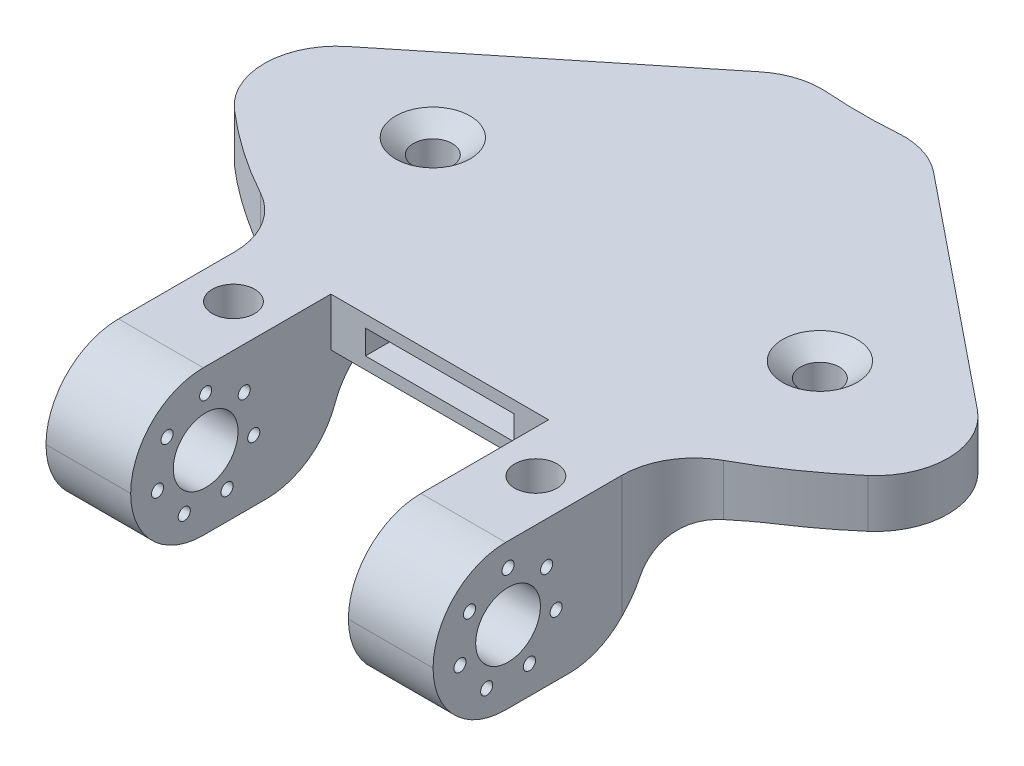
SolidWorks part; units mm, degrees
ref_plane "Front Plane" through (0, 0, 0) normal (0, 0, 1) x (1, 0, 0)
ref_plane "Top Plane" through (0, 0, 0) normal (0, 1, 0) x (1, 0, 0)
ref_plane "Right Plane" through (0, 0, 0) normal (1, 0, 0) x (0, 0, -1)
sketch "Sketch1" plane through (0, 0, 0) normal (0, 1, 0) x (1, 0, 0)
  line L0 (-41.3294, -33.3834) -> (-11.3979, -9.2065)
  line L1 (0, 0) -> (0, -63.5) construction
  line L2 (41.3294, -33.3834) -> (11.3979, -9.2065)
  line L3 (0, -63.5) -> (0, -88.9) construction
  line L4 (-25.4, -88.9) -> (-14.2875, -88.9)
  line L5 (25.4, -88.9) -> (25.4, -64.1319)
  line L6 (-25.4, -88.9) -> (-25.4, -64.1319)
  line L7 (25.4, -58.1987) -> (25.4, -60.8499) construction
  line L8 (-25.4, -58.1987) -> (-25.4, -60.8499) construction
  line L9 (-14.2875, -88.9) -> (-14.2875, -62.6241)
  line L10 (-14.2875, -68.9741) -> (14.2875, -68.9741) construction
  line L11 (14.2875, -88.9) -> (14.2875, -62.6241)
  line L12 (-14.2875, -88.9) -> (0, -88.9) construction
  line L13 (14.2875, -88.9) -> (25.4, -88.9)
  line L14 (0, -88.9) -> (14.2875, -88.9) construction
  line L15 (-14.2875, -62.6241) -> (14.2875, -62.6241)
  arc A1 (-41.5815, -47.992) -> (-30.3696, -55.7668) centre (0, 0) ccw
  arc A2 (-4.7067, -7.1174) -> (4.7067, -7.1174) centre (0, 56.2079) ccw
  arc A3 (-56.9422, 28.1039) -> (-49.3981, -39.9009) centre (0, 0) ccw construction
  arc A4 (-56.9422, 28.1039) -> (-8.3458, -6.7413) centre (0, 56.2079) ccw construction
  arc A5 (8.3458, -6.7413) -> (56.9422, 28.1039) centre (0, 56.2079) ccw construction
  arc A6 (56.9422, 28.1039) -> (-56.9422, 28.1039) centre (0, 56.2079) ccw construction
  arc A7 (49.3981, -39.9009) -> (56.9422, 28.1039) centre (0, 0) ccw construction
  arc A8 (56.9422, 28.1039) -> (-56.9422, 28.1039) centre (0, 0) ccw construction
  arc A9 (41.3294, -33.3834) -> (41.5815, -47.992) centre (35.3443, -40.7932) cw
  arc A10 (-41.3294, -33.3834) -> (-41.5815, -47.992) centre (-35.3443, -40.7932) ccw
  arc A11 (-11.3979, -9.2065) -> (-4.7067, -7.1174) centre (-5.4127, -16.6162) cw
  arc A12 (11.3979, -9.2065) -> (4.7067, -7.1174) centre (5.4127, -16.6162) ccw
  arc A13 (0, -63.5) -> (25.4, -58.1987) centre (0, 0) ccw construction
  arc A14 (30.3696, -55.7668) -> (41.5815, -47.992) centre (0, 0) ccw
  arc A15 (-25.4, -58.1987) -> (0, -63.5) centre (0, 0) ccw construction
  arc A16 (30.3696, -55.7668) -> (25.4, -64.1319) centre (34.925, -64.1319) ccw
  arc A17 (-30.3696, -55.7668) -> (-25.4, -64.1319) centre (-34.925, -64.1319) cw
  point P33 (0, -68.9741)
  dimension "D1" = 127
  dimension "D2" = 127
  dimension "D3" = 9.525
  dimension "D7" = 9.525
  dimension "D4" = 50.8
  dimension "D5" = 25.4
  dimension "D6" = 28.575
  dimension "D8" = 6.35
extrude "Boss-Extrude1" add sketch "Sketch1" along normal blind 19.05
sketch "Sketch2" plane through (-25.4, 0, 0) normal (-1, 0, 0) x (0, 0, 1)
  line L0 (88.9, 9.525) -> (79.0575, 9.525) construction
  line L1 (88.9, 19.05) -> (88.9, 0) construction
  circle A0 centre (79.0575, 9.525) radius 4.25
  dimension "D1" = 8.5
  dimension "D2" = 9.8425
extrude "Cut-Extrude1" cut sketch "Sketch2" against normal through all both and the other way through all
fillet "Fillet1" radius 9.525 4 edges at (19.8438, 0, 88.9) (-19.8437, 0, 88.9) (19.8438, 19.05, 88.9) (-19.8437, 19.05, 88.9)
sketch "Sketch3" plane through (0, 0, 0) normal (0, -1, 0) x (1, 0, 0)
  line L0 (25.5201, 62.6241) -> (-25.5201, 62.6241)
  line L1 (14.2875, 62.6241) -> (-14.2875, 62.6241)
  line L2 (-25.4, 79.375) -> (-25.4, 62.6241) construction
  line L3 (25.4, 62.6241) -> (25.4, 79.375) construction
  line L9 (25.4, 64.1319) -> (25.4, 79.375)
  line L10 (25.4, 79.375) -> (14.2875, 79.375)
  line L11 (14.2875, 79.375) -> (14.2875, 62.6241)
  line L12 (14.2875, 62.6241) -> (-14.2875, 62.6241)
  line L13 (-14.2875, 62.6241) -> (-14.2875, 79.375)
  line L14 (-14.2875, 79.375) -> (-25.4, 79.375)
  line L15 (-25.4, 79.375) -> (-25.4, 64.1319)
  line L16 (-41.3294, 33.3834) -> (-11.3979, 9.2065)
  line L17 (11.3979, 9.2065) -> (41.3294, 33.3834)
  line L18 (25.4, 64.1319) -> (25.4, 62.6241) construction
  line L19 (25.4, 79.375) -> (14.2875, 79.375) construction
  line L20 (14.2875, 79.375) -> (14.2875, 62.6241) construction
  line L22 (-14.2875, 62.6241) -> (-14.2875, 79.375) construction
  line L23 (-14.2875, 79.375) -> (-25.4, 79.375) construction
  line L24 (-25.4, 62.6241) -> (-25.4, 64.1319) construction
  line L25 (-41.3294, 33.3834) -> (-11.3979, 9.2065)
  line L26 (11.3979, 9.2065) -> (41.3294, 33.3834)
  arc A0 (-25.5201, 62.6241) -> (-25.4, 64.1319) centre (-34.925, 64.1319) ccw construction
  arc A1 (25.4, 64.1319) -> (25.5201, 62.6241) centre (34.925, 64.1319) ccw construction
  arc A9 (-30.3696, 55.7668) -> (-25.4, 64.1319) centre (-34.925, 64.1319) ccw
  arc A10 (-30.3696, 55.7668) -> (-41.5815, 47.992) centre (0, 0) ccw
  arc A11 (-41.5815, 47.992) -> (-41.3294, 33.3834) centre (-35.3443, 40.7932) ccw
  arc A12 (-11.3979, 9.2065) -> (-4.7067, 7.1174) centre (-5.4127, 16.6162) ccw
  arc A13 (4.7067, 7.1174) -> (-4.7067, 7.1174) centre (0, -56.2079) ccw
  arc A14 (4.7067, 7.1174) -> (11.3979, 9.2065) centre (5.4127, 16.6162) ccw
  arc A15 (41.3294, 33.3834) -> (41.5815, 47.992) centre (35.3443, 40.7932) ccw
  arc A16 (41.5815, 47.992) -> (30.3696, 55.7668) centre (0, 0) ccw
  arc A17 (25.4, 64.1319) -> (30.3696, 55.7668) centre (34.925, 64.1319) ccw
  arc A18 (-30.3696, 55.7668) -> (-25.5201, 62.6241) centre (-34.925, 64.1319) ccw
  arc A19 (-30.3696, 55.7668) -> (-41.5815, 47.992) centre (0, 0) ccw
  arc A20 (-41.5815, 47.992) -> (-41.3294, 33.3834) centre (-35.3443, 40.7932) ccw
  arc A21 (-11.3979, 9.2065) -> (-4.7067, 7.1174) centre (-5.4127, 16.6162) ccw
  arc A22 (4.7067, 7.1174) -> (-4.7067, 7.1174) centre (0, -56.2079) ccw
  arc A23 (4.7067, 7.1174) -> (11.3979, 9.2065) centre (5.4127, 16.6162) ccw
  arc A24 (41.3294, 33.3834) -> (41.5815, 47.992) centre (35.3443, 40.7932) ccw
  arc A25 (41.5815, 47.992) -> (30.3696, 55.7668) centre (0, 0) ccw
  arc A26 (25.5201, 62.6241) -> (30.3696, 55.7668) centre (34.925, 64.1319) ccw
  arc M26 (-25.4, 64.1319) -> (-30.3696, 55.7668) centre (-34.925, 64.1319) cw
  arc M27 (-30.3696, 55.7668) -> (-41.5815, 47.992) centre (0, 0) ccw
  arc M28 (-41.5815, 47.992) -> (-41.3294, 33.3834) centre (-35.3443, 40.7932) ccw
  line M29 (-41.3294, 33.3834) -> (-11.3979, 9.2065)
  arc M30 (-11.3979, 9.2065) -> (-4.7067, 7.1174) centre (-5.4127, 16.6162) ccw
  arc M31 (-4.7067, 7.1174) -> (4.7067, 7.1174) centre (0, -56.2079) cw
  arc M32 (4.7067, 7.1174) -> (11.3979, 9.2065) centre (5.4127, 16.6162) ccw
  line M33 (11.3979, 9.2065) -> (41.3294, 33.3834)
  arc M34 (41.3294, 33.3834) -> (41.5815, 47.992) centre (35.3443, 40.7932) ccw
  arc M35 (41.5815, 47.992) -> (30.3696, 55.7668) centre (0, 0) ccw
  arc M36 (30.3696, 55.7668) -> (25.4, 64.1319) centre (34.925, 64.1319) cw
  line M38 (14.2875, 62.6241) -> (-14.2875, 62.6241)
  dimension "D1" = 0
extrude "Cut-Extrude2" cut sketch "Sketch3" against normal offset from surface (12.7 mm away) 6.35 contours L0 M36 M38 M26 M27 M28 M29 M30 M31 M32 M33 M34 M35 region at (0, 0, 37.8623) up to face at (0, 19.05, 48.6647)
fillet "Fillet2" radius 9.525 2 edges at (19.9038, 12.7, 62.6241) (-19.9038, 12.7, 62.6241)
fillet "Fillet3" radius 9.525 2 edges at (-19.9038, 0, 62.6241) (19.9038, 0, 62.6241)
hole_wizard "PlateMount - CSK for #10 Flat Head Machine Screw (100)2" positions "Sketch4" profile "Sketch5" countersink size "#10" standard "ANSI Inch" end condition up to next
sketch "Sketch4" plane through (0, 19.05, 0) normal (0, 1, 0) x (1, 0, 0)
  line L0 (0, -68.9741) -> (0, -7.2921) construction
  line L2 (-25.4, -38.1331) -> (25.4, -38.1331) construction
  arc A0 (-4.7067, -7.1174) -> (4.7067, -7.1174) centre (0, 56.2079) ccw construction
  point P12 (25.4, -38.1331)
  point P14 (-25.4, -38.1331)
  dimension "D1" = 50.8
  dimension "D2" = 38.1331
sketch "Sketch5" plane through (-25.4, 19.05, 38.1331) normal (1, 0, 0) x (0, 0, 1)
  line L0 (0, 0) -> (0, 6.35)
  line L1 (0, 6.35) -> (2.5527, 6.35)
  line L2 (2.5527, 6.35) -> (2.5527, 1.9608)
  line L3 (2.5527, 1.9608) -> (4.8895, 0)
  line L5 (4.8895, 0) -> (0, 0)
  line L6 (-2.5527, 1.9608) -> (-4.8895, 0) construction
  line L11 (0, -6.35) -> (0, 107.95) construction
  dimension "Thru Hole Dia." = 5.1054
  dimension "Thru Hole Depth" = 6.35
  dimension "Near C'Sink Dia." = 9.779
  dimension "Near C'Sink Angle" = 100
sketch "Sketch6" plane through (0, 0, 0) normal (0, -1, 0) x (1, 0, 0)
  line L0 (-19.8437, 79.375) -> (-19.8437, 69.85) construction
  line L1 (-14.2875, 79.375) -> (-25.4, 79.375) construction
  line L2 (-19.8437, 79.375) -> (19.8438, 79.375) construction
  line L3 (25.4, 79.375) -> (14.2875, 79.375) construction
  line L4 (0, 79.375) -> (0, 50.9244) construction
  circle A0 centre (-19.8437, 69.85) radius 2.7781
  circle A1 centre (19.8437, 69.85) radius 2.7781
  dimension "D2" = 5.5562
  dimension "D1" = 9.525
extrude "MagnetPilotHoles" cut sketch "Sketch6" against normal through all both and the other way through all
sketch "Sketch7" plane through (-25.4, 0, 0) normal (-1, 0, 0) x (0, 0, 1)
  circle A1 centre (79.0575, 15.9975) radius 0.7937
  circle A2 centre (79.0575, 9.525) radius 6.4725
  circle A3 centre (79.0575, 9.525) radius 6.4725 construction
  circle A4 centre (84.1179, 13.5605) radius 0.7937
  circle A5 centre (85.3677, 8.0847) radius 0.7937
  circle A6 centre (81.8658, 3.6935) radius 0.7937
  circle A7 centre (76.2492, 3.6935) radius 0.7937
  circle A8 centre (72.7473, 8.0847) radius 0.7937
  circle A9 centre (73.9971, 13.5605) radius 0.7937
  point P19 (79.0575, 9.525)
  dimension "D2" = 1.5875
  dimension "D1" = 2.2225
  dimension "D3" = 7
extrude "ConcentricSpring" cut sketch "Sketch7" against normal through all
sketch "Sketch8" plane through (0, 0, 62.6241) normal (0, 0, 1) x (1, 0, 0)
  line L0 (0, 19.05) -> (0, 15.875) construction
  line L1 (-14.2875, 19.05) -> (14.2875, 19.05) construction
  line L3 (-9.7531, 17.4625) -> (9.7531, 17.4625)
  line L4 (-9.7531, 17.4625) -> (-9.7531, 14.2875)
  line L5 (-9.7531, 14.2875) -> (9.7531, 14.2875)
  line L6 (9.7531, 17.4625) -> (9.7531, 14.2875)
  line L7 (-9.7531, 17.4625) -> (9.7531, 14.2875) construction
  line L8 (-9.7531, 14.2875) -> (9.7531, 17.4625) construction
  dimension "D1" = 3.175
  dimension "D2" = 3.175
extrude "FlatSpring" cut sketch "Sketch8" against normal blind 12.7
